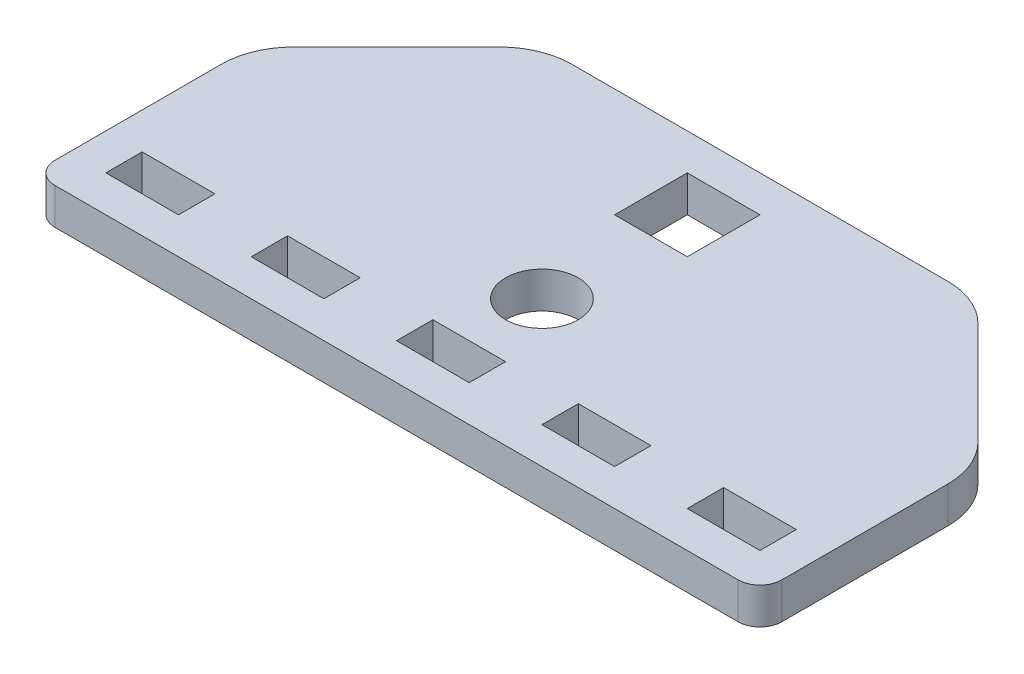
SolidWorks part; units mm, degrees
material "Maple"
ref_plane "Front" through (0, 0, 0) normal (0, 0, 1) x (1, 0, 0)
ref_plane "Top" through (0, 0, 0) normal (0, 1, 0) x (1, 0, 0)
ref_plane "Right" through (0, 0, 0) normal (1, 0, 0) x (0, 0, -1)
sketch "Sketch2" plane through (0, 0, 0) normal (0, 1, 0) x (1, 0, 0)
  line L0 (-12.5, -10) -> (-12.5, -7.5)
  line L1 (-25, -12.5) -> (25, -12.5) construction
  line L2 (-25, -12.5) -> (-25, 12.5) construction
  line L3 (-25, 12.5) -> (25, 12.5) construction
  line L4 (25, -12.5) -> (25, 12.5) construction
  line L5 (-25, -12.5) -> (25, 12.5) construction
  line L6 (-25, 12.5) -> (25, -12.5) construction
  line L7 (-22.5, -10) -> (-17.5, -10)
  line L8 (-22.5, -10) -> (-22.5, -7.5)
  line L9 (-22.5, -7.5) -> (-17.5, -7.5)
  line L10 (-17.5, -10) -> (-17.5, -7.5)
  line L11 (-22.5, -10) -> (-17.5, -7.5) construction
  line L12 (-22.5, -7.5) -> (-17.5, -10) construction
  line L13 (-12.5, -10) -> (-7.5, -10)
  line L14 (-7.5, -10) -> (-7.5, -7.5)
  line L15 (-12.5, -7.5) -> (-7.5, -7.5)
  line L16 (-2.5, -10) -> (-2.5, -7.5)
  line L17 (-2.5, -10) -> (2.5, -10)
  line L18 (2.5, -10) -> (2.5, -7.5)
  line L19 (-2.5, -7.5) -> (2.5, -7.5)
  line L20 (7.5, -10) -> (7.5, -7.5)
  line L21 (7.5, -10) -> (12.5, -10)
  line L22 (12.5, -10) -> (12.5, -7.5)
  line L23 (7.5, -7.5) -> (12.5, -7.5)
  line L24 (17.5, -10) -> (17.5, -7.5)
  line L25 (17.5, -10) -> (22.5, -10)
  line L26 (22.5, -10) -> (22.5, -7.5)
  line L27 (17.5, -7.5) -> (22.5, -7.5)
  line L28 (-23.5355, 3.9645) -> (-16.4645, 11.0355)
  line L29 (-2.5, 5) -> (2.5, 5)
  line L30 (-2.5, 5) -> (-2.5, 10)
  line L31 (-2.5, 10) -> (2.5, 10)
  line L32 (2.5, 5) -> (2.5, 10)
  line L33 (-2.5, 5) -> (2.5, 10) construction
  line L34 (-2.5, 10) -> (2.5, 5) construction
  line L35 (-23.5, -12.5) -> (23.5, -12.5)
  line L36 (-25, -11) -> (-25, 0.4289)
  line L37 (-12.9289, 12.5) -> (12.9289, 12.5)
  line L38 (25, -11) -> (25, 0.4289)
  line L39 (-25, -12.5) -> (25, 12.5) construction
  line L40 (-25, 12.5) -> (25, -12.5) construction
  line L41 (16.4645, 11.0355) -> (23.5355, 3.9645)
  circle A0 centre (0, -2.5) radius 2.5
  arc A1 (23.5355, 3.9645) -> (25, 0.4289) centre (20, 0.4289) cw
  arc A2 (16.4645, 11.0355) -> (12.9289, 12.5) centre (12.9289, 7.5) ccw
  arc A3 (-16.4645, 11.0355) -> (-12.9289, 12.5) centre (-12.9289, 7.5) cw
  arc A4 (-23.5355, 3.9645) -> (-25, 0.4289) centre (-20, 0.4289) ccw
  arc A5 (23.5, -12.5) -> (25, -11) centre (23.5, -11) ccw
  arc A6 (-23.5, -12.5) -> (-25, -11) centre (-23.5, -11) cw
  point P0 (0, 0)
  point P6 (-20, -8.75)
  point P11 (-17.5, -8.75)
  point P12 (0, 7.5)
  point P34 (0, 0)
  point P40 (0, 0)
  point P41 (0, 0)
  point P42 (0, 0)
  point P45 (25, 2.5)
  point P48 (15, 12.5)
  point P51 (-15, 12.5)
  point P54 (-25, 2.5)
  dimension "D12" = 5
  dimension "D13" = 5
  dimension "D16" = 1.5
  dimension "D1" = 25
  dimension "D2" = 50
  dimension "D3" = 2.5
  dimension "D4" = 2.5
  dimension "D5" = 5
  dimension "D6" = 2.5
  dimension "D8" = 5
  dimension "D9" = 5
  dimension "D10" = 5
  dimension "D11" = 2.5
  dimension "D7" = 5
extrude "Boss-Extrude1" add sketch "Sketch2" along normal blind 2.5 contours A6 L35 A5 L38 A1 L41 A2 L37 A3 L28 A4 L36 A0 L32 L29 L30 L31 L10 L7 L8 L9 L0 L15 L14 L13 L16 L19 L18 L17 L20 L23 L22 L21 L24 L27 L26 L25 region at (-19.6047, 0, -7.1047)
